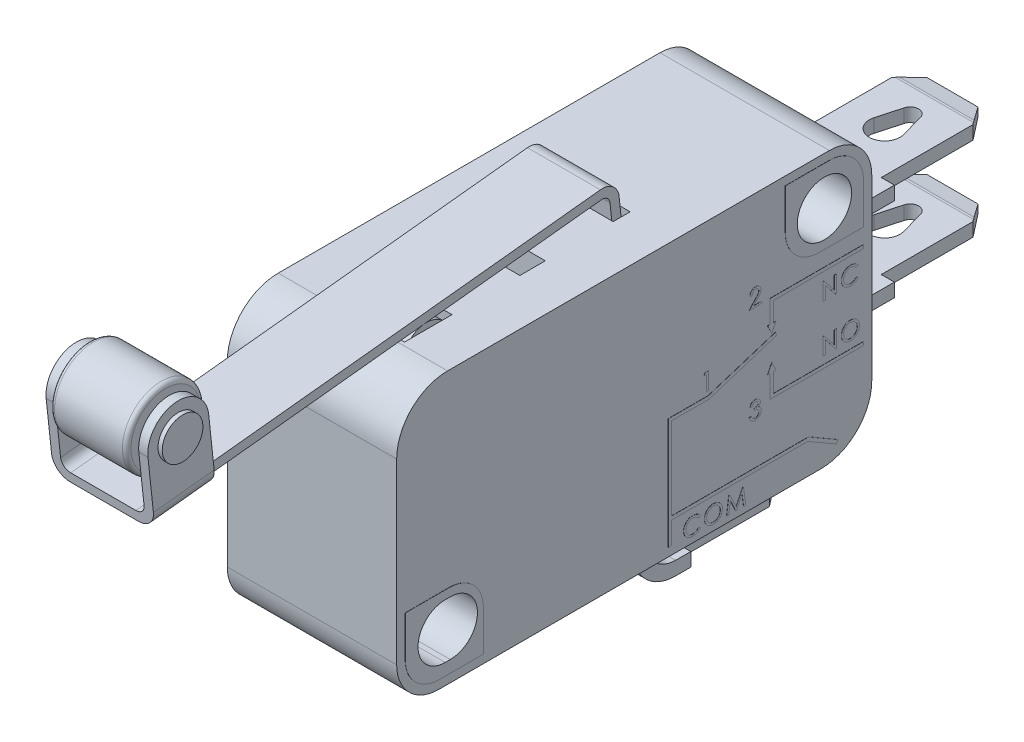
SolidWorks part; units mm, degrees
other "Switch Body"
other "Connections"
other "Lever with Wheel"
material "ABS"
ref_plane "Front Plane" through (0, 0, 0) normal (0, 0, 1) x (1, 0, 0)
ref_plane "Top Plane" through (0, 0, 0) normal (0, 1, 0) x (1, 0, 0)
ref_plane "Right Plane" through (0, 0, 0) normal (1, 0, 0) x (0, 0, -1)
sketch "Sketch1" plane through (0, 0, 0) normal (1, 0, 0) x (0, 0, -1)
  line L0 (-14, 0) -> (0, 0) construction
  line L1 (-11, 8) -> (11.5, 8)
  line L2 (-14, 5) -> (-14, -5.5)
  line L3 (-11.5, -8) -> (11, -8)
  line L4 (14, 5.5) -> (14, -5)
  line L5 (0, 0) -> (14, 0) construction
  line L6 (0, 0) -> (0, -8) construction
  line L7 (0, 0) -> (0, 8) construction
  arc A0 (-11, 8) -> (-14, 5) centre (-11, 5) ccw
  arc A1 (11, -8) -> (14, -5) centre (11, -5) ccw
  arc A2 (-14, -5.5) -> (-11.5, -8) centre (-11.5, -5.5) ccw
  arc A3 (11.5, 8) -> (14, 5.5) centre (11.5, 5.5) cw
  dimension "D3" = 3
  dimension "D4" = 2.5
  dimension "D1" = 28
  dimension "D2" = 16
extrude "Body Extrude" add sketch "Sketch1" along normal mid plane 9.98
sketch "Sketch4" plane through (4.99, 0, 0) normal (1, 0, 0) x (0, 0, -1)
  line L0 (-11.15, -5.2) -> (-10.85, -5.2) construction
  line L1 (-11.15, -3.6) -> (-10.85, -3.6)
  line L2 (-11.15, -6.8) -> (-10.85, -6.8)
  line L3 (-11.15, -5.2) -> (-12.75, -5.2) construction
  line L4 (-10.85, -5.2) -> (-9.25, -5.2) construction
  line L5 (11.2, 5.2) -> (11.2, 6.8) construction
  line L6 (11.2, 6.8) -> (11.2, 8) construction
  line L7 (11.5, 8) -> (-11, 8) construction
  line L8 (11.2, 5.2) -> (12.8, 5.2) construction
  line L9 (12.8, 5.2) -> (14, 5.2) construction
  line L10 (14, -5) -> (14, 5.5) construction
  line L11 (11.2, 5.2) -> (11.2, 3.6) construction
  line L13 (-11.5, -8) -> (11, -8) construction
  line L15 (-14, 5) -> (-14, -5.5) construction
  circle A0 centre (11.2, 5.2) radius 1.6
  arc A1 (-11.15, -3.6) -> (-11.15, -6.8) centre (-11.15, -5.2) ccw
  arc A2 (-10.85, -6.8) -> (-10.85, -3.6) centre (-10.85, -5.2) ccw
  point P4 (-11, -5.2)
  dimension "D1" = 3.2
  dimension "D2" = 3.2
  dimension "D3" = 3.5
  dimension "D4" = 1.2
  dimension "D5" = 1.2
  dimension "D6" = 2.8
  dimension "D7" = 2.8
  dimension "D8" = 11.6
  dimension "D9" = 1.2
  dimension "D10" = 3
  dimension "D11" = 2.8
  dimension "D12" = 11.6
extrude "Mount Holes Cut" cut sketch "Sketch4" against normal up to surface (9.98 mm away) up to face at (-4.99, 0, 0)
sketch "Sketch3" plane through (0, 0, 0) normal (1, 0, 0) x (0, 0, -1)
  line L0 (23.75, 2.5) -> (1.75, 2.5)
  line L1 (1.75, 2.5) -> (1.75, -11)
  line L2 (1.75, -11) -> (11.75, -11)
  line L3 (11.75, -11) -> (11.75, -10.2)
  line L4 (11.75, -10.2) -> (2.55, -10.2)
  line L5 (2.55, -10.2) -> (2.55, -3.25)
  line L6 (2.55, -3.25) -> (23.75, -3.25)
  line L7 (23.75, -3.25) -> (23.75, -2.45)
  line L8 (23.75, -2.45) -> (2.55, -2.45)
  line L9 (2.55, -2.45) -> (2.55, 1.7)
  line L10 (2.55, 1.7) -> (23.75, 1.7)
  line L11 (23.75, 1.7) -> (23.75, 2.5)
  line L12 (23.75, -2.45) -> (23.75, 1.7) construction
  line L13 (2.55, -2.45) -> (2.55, -3.25) construction
  line L14 (11.75, -11) -> (23.75, -11) construction
  line L15 (23.75, -11) -> (23.75, -3.25) construction
  line L16 (11.75, -10.2) -> (23.75, -10.2) construction
  line L17 (14, -5) -> (14, 5.5) construction
  line L18 (11.5, 8) -> (-11, 8) construction
  dimension "D1" = 0.8
  dimension "D2" = 0.8
  dimension "D3" = 10
  dimension "D4" = 12
  dimension "D5" = 5.75
  dimension "D6" = 9.75
  dimension "D7" = 19
  dimension "D8" = 5.5
extrude "Connection Extrude" add sketch "Sketch3" along normal mid plane 6.35 separate body
sketch "Sketch6" plane through (0, 0, -14) normal (0, 0, -1) x (-1, 0, 0)
  line L4 (3.175, 1.7) -> (3.175, 2.5)
  line L5 (3.175, 2.5) -> (-3.175, 2.5)
  line L6 (-3.175, 2.5) -> (-3.175, 1.7)
  line L7 (-3.175, 1.7) -> (3.175, 1.7)
  line L8 (3.175, 1.7) -> (3.175, 2.5)
  line L9 (3.175, 2.5) -> (-3.175, 2.5)
  line L10 (-3.175, 2.5) -> (-3.175, 1.7)
  line L11 (-3.175, 1.7) -> (3.175, 1.7)
  line L12 (3.175, -3.25) -> (3.175, -2.45)
  line L13 (3.175, -2.45) -> (-3.175, -2.45)
  line L14 (-3.175, -2.45) -> (-3.175, -3.25)
  line L15 (-3.175, -3.25) -> (3.175, -3.25)
  line L16 (3.175, -3.25) -> (3.175, -2.45)
  line L17 (3.175, -2.45) -> (-3.175, -2.45)
  line L18 (-3.175, -2.45) -> (-3.175, -3.25)
  line L19 (-3.175, -3.25) -> (3.175, -3.25)
  dimension "D1" = 0
  dimension "D2" = 0
extrude "Connection Cut-1" cut sketch "Sketch6" against normal blind 0.5
sketch "Sketch7" plane through (0, -8, 0) normal (0, -1, 0) x (1, 0, 0)
  line L0 (3.175, -1.75) -> (-3.175, -1.75) construction
  line L1 (-3.175, -1.75) -> (3.175, -1.75)
  line L2 (-3.175, -1.75) -> (-3.175, -2.55)
  line L3 (-3.175, -2.55) -> (3.175, -2.55)
  line L4 (3.175, -1.75) -> (3.175, -2.55)
  line L5 (3.175, -1.75) -> (3.175, -11.75) construction
  line L6 (-3.175, -1.75) -> (-3.175, -11.75) construction
  dimension "D1" = 0.8
extrude "Connection Cut-2" cut sketch "Sketch7" against normal blind 0.5
fillet "Connection Fillet-1" radius 2.5 1 edges at (0, -11, -1.75)
fillet "Connection Fillet-2" radius 1.7 1 edges at (0, -10.2, -2.55)
sketch "Sketch5" plane through (3.175, 0, 0) normal (1, 0, 0) x (0, 0, -1)
  line L0 (23.75, 2.1) -> (22.75, 2.1) construction
  line L1 (23.75, 1.7) -> (23.75, 2.5) construction
  line L2 (23.75, -2.85) -> (22.75, -2.85) construction
  line L3 (23.75, -3.25) -> (23.75, -2.45) construction
  line L4 (11.75, -10.6) -> (10.75, -10.6) construction
  line L5 (11.75, -11) -> (11.75, -10.2) construction
  line L6 (10.75, -11) -> (10.75, -10.2) construction
  line L7 (11.75, -10.2) -> (4.25, -10.2) construction
  line L8 (22.75, -2.45) -> (22.75, -3.25) construction
  line L9 (23.75, -2.45) -> (2.55, -2.45) construction
  line L10 (22.75, 2.5) -> (22.75, 1.7) construction
  line L11 (23.75, 2.5) -> (1.75, 2.5) construction
  line L12 (11.75, -10.35) -> (11.75, -10.85) construction
  line L13 (23.75, 2.35) -> (23.75, 1.85) construction
  line L14 (23.75, -2.6) -> (23.75, -3.1) construction
  line L15 (10.75, -10.2) -> (11.75, -10.2)
  line L16 (11.75, -10.2) -> (11.75, -10.35)
  line L17 (11.75, -10.35) -> (10.75, -10.2)
  line L18 (10.75, -11) -> (11.75, -11)
  line L19 (11.75, -11) -> (11.75, -10.85)
  line L20 (11.75, -10.85) -> (10.75, -11)
  line L21 (22.75, 2.5) -> (23.75, 2.5)
  line L22 (23.75, 2.5) -> (23.75, 2.35)
  line L23 (23.75, 2.35) -> (22.75, 2.5)
  line L24 (22.75, 1.7) -> (23.75, 1.7)
  line L25 (23.75, 1.7) -> (23.75, 1.85)
  line L26 (23.75, 1.85) -> (22.75, 1.7)
  line L27 (22.75, -2.45) -> (23.75, -2.45)
  line L28 (23.75, -2.45) -> (23.75, -2.6)
  line L29 (23.75, -2.6) -> (22.75, -2.45)
  line L30 (22.75, -3.25) -> (23.75, -3.25)
  line L31 (23.75, -3.25) -> (23.75, -3.1)
  line L32 (23.75, -3.1) -> (22.75, -3.25)
  dimension "D1" = 0.5
  dimension "D2" = 1
extrude "Connection Cut-3" cut sketch "Sketch5" against normal up to surface (6.35 mm away) up to face at (-3.175, -4.5193, -9.9879)
fillet "Connection Fillet-3" radius 1 6 edges at (0, 2.5, -22.75) (0, 1.7, -22.75) (0, -3.25, -22.75) (0, -2.45, -22.75) (0, -10.2, -10.75) (0, -11, -10.75)
sketch "Sketch8" plane through (0, -11, 0) normal (0, -1, 0) x (1, 0, 0)
  line L0 (0, 0) -> (0, -5.15) construction
  line L1 (0, -5.15) -> (0, -8.5) construction
  line L2 (0, -8.5) -> (0, -11.75) construction
  line L3 (-3.175, -11.75) -> (3.175, -11.75) construction
  line L4 (2.4, -5.15) -> (-2.4, -5.15) construction
  line L5 (1.5, -11.75) -> (-1.5, -11.75) construction
  line L6 (-2.4, -5.15) -> (-3.175, -5.15)
  line L7 (-3.175, -4.25) -> (-3.175, -10.6754) construction
  line L8 (-3.175, -5.15) -> (-3.175, -11.75)
  line L9 (-3.175, -10.8238) -> (-3.175, -11.75) construction
  line L10 (2.4, -5.15) -> (3.175, -5.15)
  line L11 (3.175, -4.25) -> (3.175, -10.6754) construction
  line L12 (3.175, -5.15) -> (3.175, -11.75)
  line L13 (-2.4, -5.15) -> (-2.4, -10.55)
  line L14 (-2.4, -10.55) -> (-1.5, -11.75)
  line L15 (2.4, -5.15) -> (2.4, -10.55)
  line L16 (2.4, -10.55) -> (1.5, -11.75)
  line L17 (-2.4, -10.55) -> (-3.175, -10.55) construction
  line L18 (2.4, -10.55) -> (3.175, -10.55) construction
  line L19 (-3.175, -11.75) -> (-1.5, -11.75)
  line L20 (1.5, -11.75) -> (3.175, -11.75)
  circle A0 centre (0, -8.5) radius 0.75
  dimension "D1" = 3
  dimension "D6" = 1.5
  dimension "D2" = 4.8
  dimension "D3" = 1.2
  dimension "D4" = 6.6
  dimension "D5" = 3.25
extrude "Connection Cut-4" cut sketch "Sketch8" against normal up to surface (0.8 mm away) up to face at (0, -10.2, -7.4627)
sketch "Sketch9" plane through (0, 8, 0) normal (0, 1, 0) x (1, 0, 0)
  line L0 (0, -14) -> (0, -10.8) construction
  line L1 (4.99, -14) -> (-4.99, -14) construction
  line L2 (0, -10.8) -> (0, -8) construction
  line L3 (-2.25, -8) -> (2.25, -8)
  line L4 (-2.25, -8) -> (-2.25, -10.8)
  line L5 (-2.25, -10.8) -> (2.25, -10.8)
  line L6 (2.25, -8) -> (2.25, -10.8)
  line L7 (0, -8) -> (0, -4) construction
  line L8 (0, -4) -> (0, -2.5) construction
  line L9 (-2.25, -2.5) -> (2.25, -2.5)
  line L10 (-2.25, -2.5) -> (-2.25, -4)
  line L11 (-2.25, -4) -> (2.25, -4)
  line L12 (2.25, -2.5) -> (2.25, -4)
  line L13 (0, -2.5) -> (0, 2) construction
  line L15 (-2.25, 2.5) -> (2.25, 2.5)
  line L16 (-2.25, 2.5) -> (-2.25, 1.5)
  line L17 (-2.25, 1.5) -> (2.25, 1.5)
  line L18 (2.25, 2.5) -> (2.25, 1.5)
  line L19 (-2.25, 2.5) -> (2.25, 1.5) construction
  line L20 (-2.25, 1.5) -> (2.25, 2.5) construction
  dimension "D1" = 2.8
  dimension "D2" = 4.5
  dimension "D3" = 6
  dimension "D4" = 10
  dimension "D5" = 1.5
  dimension "D6" = 16
  dimension "D7" = 1
extrude "Button Cut-1" cut sketch "Sketch9" against normal blind 4
sketch "Sketch10" plane through (0, 2.5, 0) normal (0, 1, 0) x (1, 0, 0)
  line L0 (0, 0) -> (0, 17.15) construction
  line L1 (0, 17.15) -> (0, 23.75) construction
  line L2 (-3.175, 23.75) -> (3.175, 23.75) construction
  line L3 (-2.4, 17.15) -> (2.4, 17.15) construction
  line L4 (-1.5, 23.75) -> (1.5, 23.75) construction
  line L5 (2.4, 17.15) -> (3.175, 17.15)
  line L6 (3.175, 22.6754) -> (3.175, 1.75) construction
  line L7 (3.175, 17.15) -> (3.175, 23.75)
  line L8 (3.175, 23.75) -> (1.5, 23.75)
  line L9 (1.5, 23.75) -> (2.4, 22.55)
  line L10 (2.4, 22.55) -> (2.4, 17.15)
  line L11 (-1.5, 23.75) -> (-2.4, 22.55)
  line L12 (-2.4, 22.55) -> (-2.4, 17.15)
  line L13 (-2.4, 17.15) -> (-3.175, 17.15)
  line L14 (-3.175, 22.6754) -> (-3.175, 1.75) construction
  line L15 (-3.175, 17.15) -> (-3.175, 23.75)
  line L16 (-3.175, 23.75) -> (-1.5, 23.75)
  line L17 (-0.4819, 21.3833) -> (-0.8674, 19.99)
  line L18 (0.4819, 21.3833) -> (0.8674, 19.99)
  arc A0 (-0.8674, 19.99) -> (0.8674, 19.99) centre (0, 19.75) ccw
  arc A1 (0.4819, 21.3833) -> (-0.4819, 21.3833) centre (0, 21.25) ccw
  dimension "D5" = 1
  dimension "D6" = 1.8
  dimension "D1" = 3
  dimension "D2" = 4.8
  dimension "D3" = 6.6
  dimension "D4" = 1.2
  dimension "D7" = 1.5
  dimension "D8" = 4
extrude "Connection Cut-5" cut sketch "Sketch10" against normal up to surface (5.75 mm away) up to face at (0, -3.25, -12.6127)
sketch "Sketch21" plane through (4.99, 0, 0) normal (1, 0, 0) x (0, 0, -1)
  line L0 (11.5, 8) -> (-11, 8) construction
  line L1 (8.9, 7.5) -> (11.5, 7.5)
  line L2 (8.9, 7.5) -> (8.9, 5.1)
  line L3 (10.9, 3.1) -> (13.5, 3.1)
  line L4 (13.5, 5.5) -> (13.5, 3.1)
  line L5 (-10.9, -3.1) -> (-13.5, -3.1)
  line L6 (-8.9, -5.1) -> (-8.9, -7.5)
  line L7 (-8.9, -7.5) -> (-11.5, -7.5)
  line L8 (-13.5, -3.1) -> (-13.5, -5.5)
  line L9 (14, -5) -> (14, 5.5) construction
  line L10 (-11.5, -8) -> (11, -8) construction
  line L11 (-14, 5) -> (-14, -5.5) construction
  line L12 (-11.15, -6.8) -> (-10.85, -6.8) construction
  line L13 (-10.85, -3.6) -> (-11.15, -3.6) construction
  line L14 (-11.15, -6.8) -> (-10.85, -6.8)
  line L15 (-10.85, -3.6) -> (-11.15, -3.6)
  arc A0 (-10.9, -3.1) -> (-8.9, -5.1) centre (-10.9, -5.1) cw
  arc A1 (8.9, 5.1) -> (10.9, 3.1) centre (10.9, 5.1) ccw
  arc A2 (11.5, 7.5) -> (13.5, 5.5) centre (11.5, 5.5) cw
  arc A3 (-11.5, -7.5) -> (-13.5, -5.5) centre (-11.5, -5.5) cw
  arc A4 (-10.85, -6.8) -> (-10.85, -3.6) centre (-10.85, -5.2) ccw construction
  arc A5 (-11.15, -3.6) -> (-11.15, -6.8) centre (-11.15, -5.2) ccw construction
  arc A6 (-10.85, -6.8) -> (-10.85, -3.6) centre (-10.85, -5.2) ccw
  arc A7 (-11.15, -3.6) -> (-11.15, -6.8) centre (-11.15, -5.2) ccw
  circle A8 centre (11.2, 5.2) radius 1.6 construction
  circle A9 centre (11.2, 5.2) radius 1.6
  dimension "D9" = 2
  dimension "D1" = 4.6
  dimension "D2" = 4.6
  dimension "D3" = 4.4
  dimension "D4" = 4.4
  dimension "D5" = 0.5
  dimension "D6" = 0.5
  dimension "D7" = 0.5
  dimension "D8" = 0.5
extrude "Mount Extension" add sketch "Sketch21" along normal blind 0.01
mirror "Mirror Mount Extension" about plane through (0, 0, 0) normal (1, 0, 0) of "Mount Extension"
sketch "Sketch22" plane through (4.99, 0, 0) normal (1, 0, 0) x (0, 0, -1)
  line L0 (23.75, 2.1) -> (14, 2.1) construction
  line L1 (23.75, 1.85) -> (23.75, 2.35) construction
  line L2 (14, -5) -> (14, 5.5) construction
  line L3 (14, 2.1) -> (13.5, 2.1) construction
  line L4 (23.75, -2.85) -> (14, -2.85) construction
  line L5 (23.75, -3.1) -> (23.75, -2.6) construction
  line L6 (14, -2.85) -> (13.5, -2.85) construction
  line L7 (13.5, 2.2) -> (13.5, 2)
  line L8 (13.5, -2.75) -> (13.5, -2.95)
  line L9 (13.5, 2.2) -> (8, 2.2)
  line L10 (13.5, -2.95) -> (8, -2.95)
  line L11 (8, 2.2) -> (8, 0.875)
  line L12 (8, -2.95) -> (8, -1.625)
  line L13 (13.5, 2) -> (8.2, 2)
  line L14 (8.2, 2) -> (8.2, 0.875)
  line L15 (8, 0.875) -> (8.2, 0.875) construction
  line L16 (13.5, -2.75) -> (8.2, -2.75)
  line L17 (8.2, -2.75) -> (8.2, -1.625)
  line L18 (8.2, -1.625) -> (8, -1.625) construction
  line L19 (8.2, 0.875) -> (8.35, 0.875)
  line L20 (8, 0.875) -> (7.85, 0.875)
  line L21 (8.1, 0.875) -> (8.1, 0.375) construction
  line L22 (7.85, 0.875) -> (8.1, 0.375)
  line L23 (8.1, 0.375) -> (8.35, 0.875)
  line L24 (8.2, -1.625) -> (8.35, -1.625)
  line L25 (8, -1.625) -> (7.85, -1.625)
  line L26 (8.1, -1.625) -> (8.1, -1.125) construction
  line L27 (7.85, -1.625) -> (8.1, -1.125)
  line L28 (8.1, -1.125) -> (8.35, -1.625)
  line L29 (-11.5, -8) -> (11, -8) construction
  line L30 (4.5, -1) -> (8.35, 0.225) construction
  line L31 (8.35, 0.225) -> (8.35, 0.875) construction
  line L32 (8.3197, 0.3203) -> (8.3803, 0.1297)
  line L33 (8.3197, 0.3203) -> (4.3631, -0.9386)
  line L34 (4.3631, -0.9386) -> (2, -0.9386)
  line L35 (2, -0.9386) -> (2, -7.5)
  line L36 (2, -7.5) -> (2.2, -7.5)
  line L37 (2.2, -7.5) -> (2.2, -6.2)
  line L38 (2.2, -1.1386) -> (4.3942, -1.1386)
  line L39 (4.3942, -1.1386) -> (8.3803, 0.1297)
  line L40 (2.2, -6) -> (10.2679, -6)
  line L41 (10.2679, -6) -> (12, -7)
  line L42 (12, -7) -> (11.9, -7.1732)
  line L43 (11.9, -7.1732) -> (10.2144, -6.2)
  line L44 (10.2144, -6.2) -> (2.2, -6.2)
  line L45 (2.2, -6) -> (2.2, -1.1386)
  line L46 (2.2, -6) -> (2.2, -6.2) construction
  circle A0 centre (4.5, -1) radius 0.15 construction
  dimension "D7" = 7
  dimension "D8" = 0.3
  dimension "D9" = 9.5
  dimension "D1" = 0.5
  dimension "D2" = 0.2
  dimension "D3" = 5.5
  dimension "D4" = 0.5
  dimension "D5" = 0.5
  dimension "D6" = 1.5
  dimension "D10" = 0.2
  dimension "D11" = 0.65
  dimension "D12" = 0.2
  dimension "D13" = 0.5
  dimension "D14" = 0.2
  dimension "D15" = 12
  dimension "D16" = 2
  dimension "D17" = 0.2
  dimension "D18" = 0.2
  dimension "D19" = 2
  dimension "D20" = 150
  dimension "D21" = 10
extrude "Schematic Lines" add sketch "Sketch22" along normal blind 0.01
sketch "Sketch23" plane through (4.99, 0, 0) normal (1, 0, 0) x (0, 0, -1)
  line L0 (8, 2.2) -> (6.25, 2.2) construction
  line L1 (5.1731, -0.6809) -> (3.4231, -0.6809) construction
  line L2 (8, -3.55) -> (6.25, -3.55) construction
  line L3 (2.55, -7.6327) -> (6.8929, -7.6327) construction
  line L4 (2.55, -8.5) -> (2.55, -3.25) construction
  line L5 (13.5, 0.5) -> (11, 0.5) construction
  line L6 (13.5, 0.5) -> (13.5, -2.3) construction
  line L7 (13.5, -2.3) -> (11, -2.3) construction
  line L8 (8, 2.2) -> (8, 0.875) construction
  line L9 (8, 2.2) -> (8, 0.875) construction
  line L10 (14, -5) -> (14, 5.5) construction
  line L11 (8.2, 2) -> (13.5, 2) construction
  line L12 (8.3197, 0.3203) -> (4.3631, -0.9386) construction
  line L13 (8, -3.55) -> (8, -2.95) construction
  text T0 "1" font "Century Gothic" height 1
  text T1 "2" font "Century Gothic" height 1
  text T2 "3" font "Century Gothic" height 1
  text T3 "COM" font "Century Gothic" height 1
  text T4 "NC" font "Century Gothic" height 1
  text T5 "NO" font "Century Gothic" height 1
  dimension "D1" = 0.5
  dimension "D2" = 1.5
  dimension "D3" = 2.8
  dimension "D4" = 2.5
  dimension "D5" = 1.75
  dimension "D6" = 0.85
  dimension "D7" = 0.6
extrude "Schematic Text" add sketch "Sketch23" along normal blind 0.01
sketch "Sketch24" plane through (-4.99, 0, 0) normal (-1, 0, 0) x (0, 0, 1)
  line L0 (-14, 2) -> (-4, 2) construction
  line L1 (-14, -5) -> (-14, 5.5) construction
  line L2 (-4, 2) -> (14, 2) construction
  line L3 (14, 5) -> (14, -5.5) construction
  line L4 (-11.5, 8) -> (11, 8) construction
  text T0 "16(5)A  250V~μ\r\n1E4  T125\r\n16A  125V~" font "Century Gothic" height 1.3
  dimension "D1" = 10
  dimension "D2" = 6
extrude "Specs Text" add sketch "Sketch24" along normal blind 0.01
sketch "Sketch11" plane through (0, 0, 0) normal (1, 0, 0) x (0, 0, -1)
  line L0 (2, 8) -> (2, 0) construction
  line L1 (2.5, 8) -> (1.5, 8) construction
  line L2 (2, 0) -> (0, 0) construction
  circle A0 centre (2, 6) radius 0.75
  dimension "D1" = 2
  dimension "D2" = 1.5
extrude "Button Cut-2" cut sketch "Sketch11" against normal mid plane 4.3
sketch "Sketch Set 0.25 or 2.75" plane through (0, 0, 0) normal (1, 0, 0) x (0, 0, -1)
  line L0 (-8, 4) -> (-10.8, 4) construction
  line L2 (-10.8, 4.25) -> (-8, 4.25)
  line L4 (-9.4, 4) -> (-9.4, 4.25) construction
  line L5 (-10.8, 4.25) -> (-10.8, 6.85)
  line L6 (-10.8, 6.85) -> (-8, 6.85) construction
  line L7 (-8, 6.85) -> (-8, 4.25)
  line L8 (-9.4, 4.25) -> (-9.4, 6.85) construction
  line L9 (-9.4, 6.85) -> (-9.4, 8.25) construction
  line L10 (11.5, 8) -> (-11, 8) construction
  arc A0 (-8, 6.85) -> (-10.8, 6.85) centre (-9.4, 6.85) ccw
  dimension "D2" = 4
  dimension "D1" = 2.8
  dimension "D3" = 0.25
extrude "Switch Button ADJUSTABLE" add sketch "Sketch Set 0.25 or 2.75" along normal mid plane 4.3 separate body
sketch "Sketch13" plane through (0, 0, 0) normal (1, 0, 0) x (0, 0, -1)
  line L0 (1.7315, 5.9712) -> (2.2685, 6.0288) construction
  line L1 (1.657, 6.667) -> (1.4118, 8.9541)
  line L2 (0.9054, 9.3625) -> (-26.2391, 6.4533)
  line L3 (2.1939, 6.7245) -> (1.9488, 9.0117)
  line L4 (0.8479, 9.8994) -> (-22.7171, 7.3738)
  line L5 (-26.2966, 6.9902) -> (-26.6654, 10.4305) construction
  line L6 (-22.7171, 7.3738) -> (-23.0859, 10.8141) construction
  line L7 (-26.6654, 10.4305) -> (-23.0859, 10.8141) construction
  line L8 (2, 6) -> (1.6803, 8.9829) construction
  line L9 (1.7315, 5.9712) -> (1.657, 6.667) construction
  line L10 (2.2685, 6.0288) -> (2.1939, 6.7245) construction
  line L11 (-22.7171, 7.3738) -> (-26.2966, 6.9902)
  line L12 (-26.2966, 6.9902) -> (-26.2391, 6.4533)
  line L13 (-24.8756, 10.6223) -> (-24.6305, 8.3354) construction
  line L14 (-24.8756, 10.6223) -> (-24.5069, 7.182) construction
  line L15 (1.4118, 8.9541) -> (1.9488, 9.0117) construction
  line L16 (-24.8756, 10.6223) -> (-25.1207, 12.9092) construction
  arc A0 (1.657, 6.667) -> (2.1939, 6.7245) centre (2, 6) ccw
  arc A2 (-23.0859, 10.8141) -> (-26.6654, 10.4305) centre (-24.8756, 10.6223) ccw construction
  arc A3 (1.9488, 9.0117) -> (0.8479, 9.8994) centre (0.9545, 8.9051) ccw
  arc A4 (1.4118, 8.9541) -> (0.9054, 9.3625) centre (0.9545, 8.9051) ccw
  circle A5 centre (-24.8756, 10.6223) radius 2.3 construction
  arc A6 (-8, 6.85) -> (-10.8, 6.85) centre (-9.4, 6.85) ccw construction
  dimension "D1" = 1.5
  dimension "D5" = 4
  dimension "D6" = 1
  dimension "D7" = 0.46
  dimension "D8" = 28.3
  dimension "D10" = 4.6
  dimension "D2" = 0.54
  dimension "D3" = 0.54
  dimension "D4" = 3.6
  dimension "D9" = 4
  dimension "D11" = 6.3
extrude "Switch Lever Extrude" add sketch "Sketch13" along normal mid plane 4.3 separate body
sketch "Sketch15" plane through (0, 9.6972, 1.0393) normal (0, 0.9943, 0.1066) x (1, 0, 0)
  line L0 (0, -25.402) -> (0, -21.552) construction
  line L1 (2.15, -25.402) -> (-2.15, -25.402) construction
  line L2 (-1.65, -21.552) -> (1.65, -21.552) construction
  line L4 (1.65, -21.552) -> (2.15, -21.552) construction
  line L5 (2.15, 1.898) -> (2.15, -25.402) construction
  line L6 (-1.65, -21.552) -> (-2.15, -21.552) construction
  line L7 (-2.15, 1.898) -> (-2.15, -25.402) construction
  line L8 (-1.9, -21.302) -> (-1.9, -21.802) construction
  line L9 (1.9, -21.302) -> (1.9, -21.802) construction
  line L10 (2.15, -21.302) -> (2.15, -21.802)
  line L11 (-2.15, -21.302) -> (-2.15, -21.802)
  line L12 (1.9, -21.302) -> (2.15, -21.302)
  line L13 (1.9, -21.802) -> (2.15, -21.802)
  line L14 (-1.9, -21.302) -> (-2.15, -21.302)
  line L15 (-1.9, -21.802) -> (-2.15, -21.802)
  arc A0 (1.9, -21.302) -> (1.9, -21.802) centre (1.9, -21.552) ccw
  arc A1 (-1.9, -21.802) -> (-1.9, -21.302) centre (-1.9, -21.552) ccw
  dimension "D1" = 3.6
  dimension "D2" = 0.5
extrude "Lever Cut-1" cut sketch "Sketch15" against normal up to surface (0.54 mm away) up to face at (0, 7.9079, 12.6668)
sketch "Sketch16" plane through (0, -2.707, 25.2574) normal (0, -0.1066, 0.9943) x (1, 0, 0)
  line L0 (2.15, 9.2127) -> (3, 9.2127)
  line L1 (3, 9.2127) -> (3, 15.0127)
  line L2 (-2.15, 9.2127) -> (-3, 9.2127)
  line L3 (-3, 9.2127) -> (-3, 15.0127)
  line L4 (-3, 15.0127) -> (-2.46, 15.0127)
  line L5 (-2.46, 15.0127) -> (-2.46, 9.7527)
  line L6 (3, 15.0127) -> (2.46, 15.0127)
  line L7 (2.46, 15.0127) -> (2.46, 9.7527)
  line L8 (2.46, 9.7527) -> (2.15, 9.7527)
  line L9 (-2.46, 9.7527) -> (-2.15, 9.7527)
  line L10 (-2.15, 9.7527) -> (-2.15, 9.2127)
  line L11 (2.15, 9.7527) -> (2.15, 9.2127)
  dimension "D1" = 6
  dimension "D2" = 5.8
extrude "Lever Side Tabs" add sketch "Sketch16" against normal up to surface (3.6 mm away) up to face at (2.025, 7.1054, 22.6884)
fillet "Lever Fillet-1" 2 edges at (2.73, 12.2203, 26.8572) (2.73, 12.6039, 23.2777) type full round first side face at (0, 9.471, 26.5625) second side face at (2.4533, 8.9382, 22.8848) middle face at (2.73, 12.4121, 25.0674)
fillet "Lever Fillet-2" 2 edges at (-2.73, 12.2203, 26.8572) (-2.73, 12.6039, 23.2777) type full round first side face at (0, 9.0236, 26.5146) second side face at (-2.4533, 8.9382, 22.8848) middle face at (-2.73, 12.4121, 25.0674)
fillet "Lever Fillet-3" radius 0.54 2 edges at (2.46, 7.182, 24.5069) (-2.46, 7.182, 24.5069)
fillet "Lever Fillet-4" radius 1 2 edges at (-3, 6.6451, 24.4494) (3, 6.6451, 24.4494)
sketch "Sketch18" plane through (0, 0, 0) normal (1, 0, 0) x (0, 0, -1)
  line L0 (-26.6654, 10.4305) -> (-23.0859, 10.8141) construction
  circle A0 centre (-24.8756, 10.6223) radius 1.2
  dimension "D1" = 2.4
extrude "Lever Shaft" add sketch "Sketch18" along normal mid plane 6.5
sketch "Sketch19" plane through (0, 0, 0) normal (1, 0, 0) x (0, 0, -1)
  circle A0 centre (-24.8756, 10.6223) radius 2.3 construction
  circle A1 centre (-24.8756, 10.6223) radius 2.3
extrude "Lever Wheel" add sketch "Sketch19" along normal mid plane 4.5
fillet "Lever Wheel Fillet-1" radius 0.25 2 edges at (-2.25, 10.6223, 22.5756) (2.25, 10.6223, 22.5756)
sketch "Sketch25" plane through (0, 0, 0) normal (1, 0, 0) x (0, 0, -1)
  line L0 (-11.5, -8) -> (11, -8) construction
  line L1 (-14, 5) -> (-14, -5.5) construction
  circle A0 centre (-2, 0) radius 3
  dimension "D1" = 6
  dimension "D2" = 8
  dimension "D3" = 12
extrude "Hollow Cut" cut sketch "Sketch25" against normal mid plane 2
sketch "Sketch26" plane through (0, 0, 0) normal (1, 0, 0) x (0, 0, -1)
  circle A0 centre (-2, 0) radius 2.05
  dimension "D1" = 4.1
extrude "Real-World Weight Adjustment" add sketch "Sketch26" along normal mid plane 2 separate body
